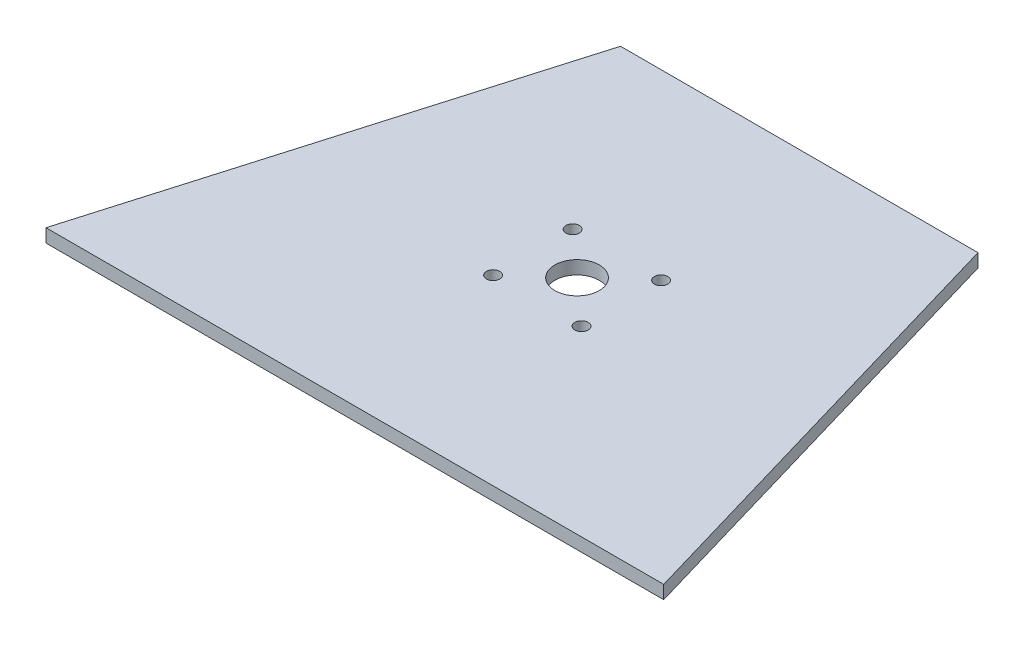
SolidWorks part; units mm, degrees
ref_plane "Front Plane" through (0, 0, 0) normal (0, 0, 1) x (1, 0, 0)
ref_plane "Top Plane" through (0, 0, 0) normal (0, 1, 0) x (1, 0, 0)
ref_plane "Right Plane" through (0, 0, 0) normal (1, 0, 0) x (0, 0, -1)
sketch "Sketch1" plane through (0, 0, 0) normal (0, 1, 0) x (1, 0, 0)
  line L0 (0, 0) -> (139, 0)
  line L1 (0, 0) -> (29.2799, 100)
  line L2 (139, 0) -> (109.7201, 100)
  line L3 (66.5, 0) -> (66.5, 100) construction
  line L4 (29.2799, 100) -> (109.7201, 100)
extrude "Boss-Extrude1" add sketch "Sketch1" along normal blind 3
hole_wizard "Ø10.0mm Dowel Hole1" positions "Sketch2" profile "Sketch3" hole size "Ø10.0" standard "ANSI Metric" end condition up to next
sketch "Sketch2" plane through (0, 0, 0) normal (0, -1, 0) x (-1, 0, 0)
  point P0 (-69.5, 50)
  point P4 (0, 0)
sketch "Sketch3" plane through (69.5, 0, -50) normal (1, 0, 0) x (0, 0, -1)
  line L0 (0, 0) -> (0, 3)
  line L1 (0, 3) -> (5, 3)
  line L2 (5, 3) -> (5, 0)
  line L5 (5, 0) -> (0, 0)
  line L11 (0, -6.35) -> (0, 107.95) construction
  dimension "Thru Hole Dia." = 10
  dimension "Thru Hole Depth" = 3
hole_wizard "Ø3.0mm Dowel Hole1" positions "Sketch4" profile "Sketch5" hole size "Ø3.0" standard "ANSI Metric" end condition up to next
sketch "Sketch4" plane through (0, 0, 0) normal (0, -1, 0) x (-1, 0, 0)
  point P0 (-59.55, 41.05)
  point P3 (-79.45, 41.05)
  point P6 (-79.45, 58.95)
  point P9 (-59.55, 58.95)
  point P13 (0, 0)
  point P14 (0, 0)
  point P15 (0, 0)
  point P16 (0, 0)
sketch "Sketch5" plane through (59.55, 0, -41.05) normal (1, 0, 0) x (0, 0, -1)
  line L0 (0, 0) -> (0, 3)
  line L1 (0, 3) -> (1.5, 3)
  line L2 (1.5, 3) -> (1.5, 0)
  line L5 (1.5, 0) -> (0, 0)
  line L11 (0, -6.35) -> (0, 107.95) construction
  dimension "Thru Hole Dia." = 3
  dimension "Thru Hole Depth" = 3
